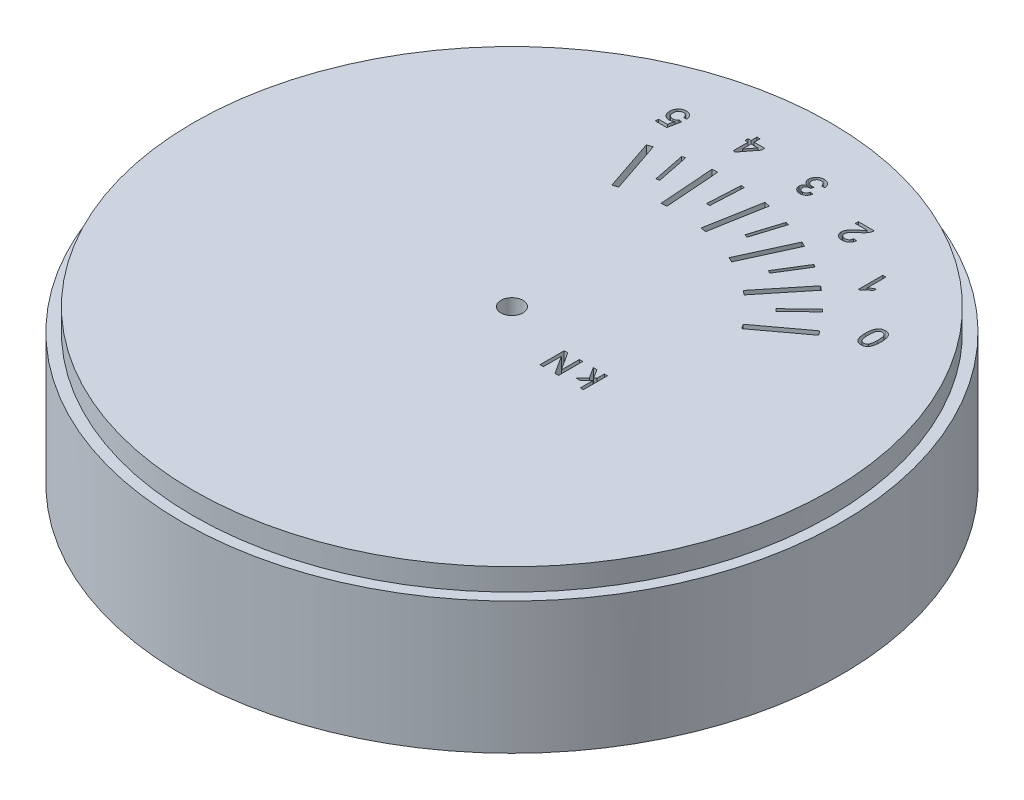
SolidWorks part; units mm, degrees
material "Chrome Stainless Steel"
ref_plane "Front Plane" through (0, 0, 0) normal (0, 0, 1) x (1, 0, 0)
ref_plane "Top Plane" through (0, 0, 0) normal (0, 1, 0) x (1, 0, 0)
ref_plane "Right Plane" through (0, 0, 0) normal (1, 0, 0) x (0, 0, -1)
sketch "Sketch1" plane through (0, 0, 0) normal (0, 1, 0) x (1, 0, 0)
  circle A0 centre (0, 0) radius 30
  dimension "D1" = 60
extrude "DIAL_CASE" add sketch "Sketch1" along normal blind 12
sketch "Sketch5" plane through (0, 12, 0) normal (0, 1, 0) x (1, 0, 0)
  circle A0 centre (0, 0) radius 29
  dimension "D1" = 58
extrude "BEZEL_SPIGOT" add sketch "Sketch5" along normal blind 2
ref_plane "Plane1" through (0, 14, 0) normal (0, 1, 0) x (1, 0, 0)
sketch "Sketch14" plane through (0, 14, 0) normal (0, 1, 0) x (1, 0, 0)
  circle A0 centre (0, 0) radius 1
  dimension "D1" = 2
extrude "Cut-Extrude8" cut sketch "Sketch14" against normal up to surface (14 mm away) up to face at (0, 0, 30)
sketch "Sketch15" plane through (0, 0, 0) normal (0, -1, 0) x (1, 0, 0)
  circle A0 centre (0, 0) radius 7.5
  dimension "D1" = 15
extrude "Cut-Extrude9" cut sketch "Sketch15" against normal blind 6 from surface starting at face at (0, 0, 1)
ref_axis "Axis1" through (0, 6, 0) along (0, -1, 0)
sketch "Sketch18" plane through (0, 0, 0) normal (0, -1, 0) x (1, 0, 0)
  line L0 (0, -7.7) -> (0, 7.7) construction
  point P0 (0, 20)
  dimension "D1" = 20
hole_wizard "CSK for M3 SFHCS1" positions "Sketch18" profile "Sketch19" countersink size "M3" standard "ANSI Metric"
sketch "Sketch19" plane through (0, 0, 20) normal (1, 0, 0) x (0, 0, -1)
  line L0 (0, 0) -> (0, 7.0215)
  line L1 (0, 7.0215) -> (1.7, 6)
  line L2 (1.7, 6) -> (1.7, 1.66)
  line L3 (1.7, 1.66) -> (3.36, 0)
  line L5 (3.36, 0) -> (0, 0)
  line L6 (-1.7, 1.66) -> (-3.36, 0) construction
  line L10 (0, 7.0215) -> (-1.7, 6) construction
  line L11 (0, -6.35) -> (0, 107.95) construction
  dimension "Hole Dia." = 3.4
  dimension "Hole Depth" = 6
  dimension "Near C'Sink Dia." = 6.72
  dimension "Near C'Sink Angle" = 90
  dimension "Drill Angle" = 118
pattern_circular "CirPattern1" count 3 over 360 about axis through (0, 6, 0) along (0, -1, 0) of "CSK for M3 SFHCS1"
sketch "Sketch20" plane through (0, 0, 0) normal (0, -1, 0) x (-1, 0, 0)
  line L0 (-7.7, 0) -> (7.7, 0) construction
  line L1 (-5, -20) -> (-12, -20)
  line L2 (-5, -20) -> (-5, 29.5804)
  line L3 (-5, 29.5804) -> (-12, 29.5804)
  line L4 (-12, -20) -> (-12, 29.5804)
  line L5 (0, 7.7) -> (0, -7.7) construction
  circle A1 centre (0, 0) radius 30 construction
  dimension "D1" = 20
  dimension "D2" = 7
  dimension "D3" = 5
extrude "Cut-Extrude11" cut sketch "Sketch20" against normal blind 6
sketch "Sketch43" plane through (0, 12, 0) normal (0, 1, 0) x (1, 0, 0)
  line L0 (11.9042, 9.1298) -> (12.2018, 8.728)
  line L1 (12.2018, 8.728) -> (16.2195, 11.7043)
  line L2 (16.2195, 11.7043) -> (15.9219, 12.106)
  line L3 (15.9219, 12.106) -> (11.9042, 9.1298)
  line L4 (9.2542, 11.8077) -> (9.6426, 11.4927)
  line L5 (9.6426, 11.4927) -> (12.7921, 15.3761)
  line L6 (12.7921, 15.3761) -> (12.4037, 15.6911)
  line L7 (12.4037, 15.6911) -> (9.2542, 11.8077)
  line L8 (6.0207, 13.741) -> (6.4752, 13.5327)
  line L9 (6.4752, 13.5327) -> (8.5579, 18.0783)
  line L10 (8.5579, 18.0783) -> (8.1033, 18.2866)
  line L11 (8.1033, 18.2866) -> (6.0207, 13.741)
  line L12 (2.4074, 14.8077) -> (2.8995, 14.7192)
  line L13 (2.8995, 14.7192) -> (3.784, 19.6404)
  line L14 (3.784, 19.6404) -> (3.2919, 19.7288)
  line L15 (3.2919, 19.7288) -> (2.4074, 14.8077)
  line L16 (-1.3577, 14.9405) -> (-0.8591, 14.9775)
  line L17 (-0.8591, 14.9775) -> (-1.2286, 19.9638)
  line L18 (-1.2286, 19.9638) -> (-1.7272, 19.9268)
  line L19 (-1.7272, 19.9268) -> (-1.3577, 14.9405)
  line L20 (-5.0372, 14.1311) -> (-4.5635, 14.2912)
  line L21 (-4.5635, 14.2912) -> (-6.1636, 19.0282)
  line L22 (-6.1636, 19.0282) -> (-6.6373, 18.8682)
  line L23 (-6.6373, 18.8682) -> (-5.0372, 14.1311)
  line L24 (12.1776, 11.8629) -> (12.3851, 11.6461)
  line L25 (12.3851, 11.6461) -> (14.5524, 13.7205)
  line L26 (14.5524, 13.7205) -> (14.3449, 13.9372)
  line L27 (14.3449, 13.9372) -> (12.1776, 11.8629)
  line L28 (8.8381, 14.5227) -> (9.093, 14.3645)
  line L29 (9.093, 14.3645) -> (10.6752, 16.9134)
  line L30 (10.6752, 16.9134) -> (10.4203, 17.0716)
  line L31 (10.4203, 17.0716) -> (8.8381, 14.5227)
  line L32 (4.9412, 16.2667) -> (5.2275, 16.177)
  line L33 (5.2275, 16.177) -> (6.1247, 19.0397)
  line L34 (6.1247, 19.0397) -> (5.8385, 19.1294)
  line L35 (5.8385, 19.1294) -> (4.9412, 16.2667)
  line L36 (0.7327, 16.9849) -> (1.0323, 16.9693)
  line L37 (1.0323, 16.9693) -> (1.188, 19.9652)
  line L38 (1.188, 19.9652) -> (0.8884, 19.9808)
  line L39 (0.8884, 19.9808) -> (0.7327, 16.9849)
  line L40 (-3.522, 16.6318) -> (-3.228, 16.6914)
  line L41 (-3.228, 16.6914) -> (-3.8236, 19.6317)
  line L42 (-3.8236, 19.6317) -> (-4.1176, 19.5721)
  line L43 (-4.1176, 19.5721) -> (-3.522, 16.6318)
  circle A0 centre (0, 0) radius 20.1312 construction
  text T0 "0" font "Arial" height 2.2
  text T1 "1" font "Arial" height 2.2
  text T2 "2" font "Arial" height 2.2
  text T3 "3" font "Arial" height 2.2
  text T4 "4" font "Arial" height 2.2
  text T5 "5" font "Arial" height 2.2
  text T6 "Nk" font "Arial" height 2.2
  dimension "D1" = 40.2625
  dimension "D2" = 5
  dimension "D3" = 0.5
  dimension "D4" = 0.3
  dimension "D5" = 3
extrude "Cut-Extrude27" cut sketch "Sketch43" along normal up to surface (2 mm away) up to face at (0, 14, 1)
